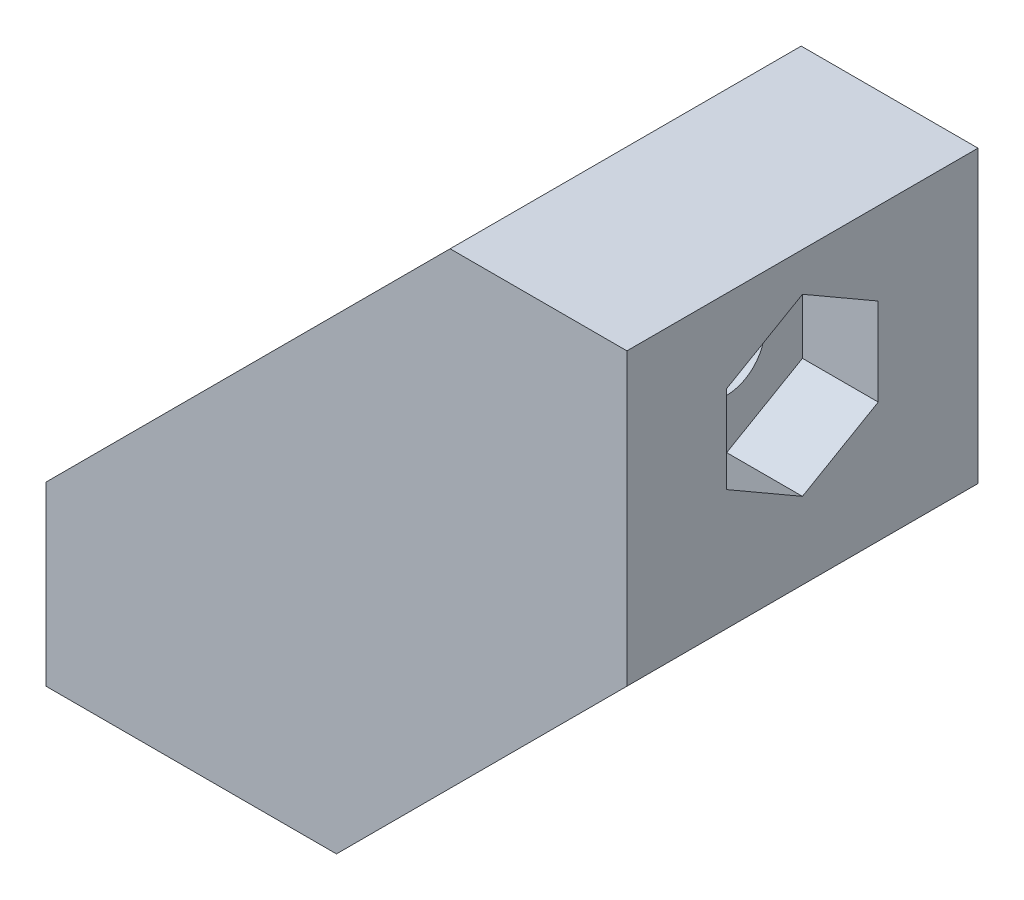
SolidWorks part; units mm, degrees
ref_plane "Front Plane" through (0, 0, 0) normal (0, 0, 1) x (1, 0, 0)
ref_plane "Top Plane" through (0, 0, 0) normal (0, 1, 0) x (1, 0, 0)
ref_plane "Right Plane" through (0, 0, 0) normal (1, 0, 0) x (0, 0, -1)
sketch "Sketch1" plane through (0, 0, 0) normal (0, 0, 1) x (1, 0, 0)
  line L0 (30, 0) -> (30, 6) construction
  line L2 (30, 0) -> (30, 8)
  line L3 (30, 8) -> (38, 8)
  line L5 (27, 0) -> (27, 6) construction
  line L6 (30, 0) -> (22, 0)
  line L8 (45, -7) -> (22, -7)
  line L9 (22, 0) -> (22, -7)
  line L11 (38, 8) -> (38, 16)
  line L12 (38, 16) -> (45, 16)
  line L13 (45, -7) -> (45, 16)
  line L14 (30, 6) -> (0, 6) construction
  line L15 (0, 0) -> (30, 0) construction
  line L16 (33.5, -7) -> (45, 4.5)
  dimension "D1" = 7
  dimension "D2" = 5
extrude "Boss-Extrude1" add sketch "Sketch1" against normal up to surface (7.9 mm away) contours L8 L16 L13 L12 L11 L3 L2 L6 L9 region at (35.0544, 2.9456, 0)
sketch "Sketch2" plane through (0, -7, 0) normal (0, -1, 0) x (1, 0, 0)
  circle A0 centre (27, -3.95) radius 1.5
  circle A1 centre (27, -3.95) radius 1.5 construction
extrude "Cut-Extrude1" cut sketch "Sketch2" against normal through all
sketch "Sketch3" plane through (38, -7, 0) normal (0, 1, 0) x (0, 0, -1)
  line L0 (0.95, 12.7321) -> (3.95, 14.4641)
  line L1 (3.95, 14.4641) -> (6.95, 12.7321)
  line L2 (6.95, 12.7321) -> (6.95, 9.2679)
  line L3 (6.95, 9.2679) -> (3.95, 7.5359)
  line L4 (3.95, 7.5359) -> (0.95, 9.2679)
  line L5 (0.95, 9.2679) -> (0.95, 12.7321)
  circle A0 centre (3.95, 11) radius 3.4641 construction
  circle A1 centre (3.95, 11) radius 1.5 construction
  point P7 (6.8792, 12.8492)
  point P10 (0, 0)
  dimension "D1" = 6
extrude "Cut-Extrude3" cut sketch "Sketch3" along normal blind 3
ref_plane "Plane1" through (19, 19, 0) normal (0.7071, 0.7071, 0) x (0.7071, -0.7071, 0)
sketch "Sketch4" plane through (0, 0, 0) normal (0, 0, 1) x (1, 0, 0)
  line L0 (22, 0) -> (38, 16)
  line L9 (22, -7) -> (33.5, -7)
  line L10 (33.5, -7) -> (45, 4.5)
  line L11 (45, 4.5) -> (45, 16)
  line L12 (45, 16) -> (38, 16)
  line L13 (38, 16) -> (38, 8)
  line L14 (38, 8) -> (30, 8)
  line L15 (30, 8) -> (30, 0)
  line L16 (30, 0) -> (22, 0)
  line L17 (22, 0) -> (22, -7)
  line L18 (22, -7) -> (33.5, -7)
  line L19 (33.5, -7) -> (45, 4.5)
  line L20 (45, 4.5) -> (45, 16)
  line L21 (45, 16) -> (38, 16)
  line L26 (22, 0) -> (22, -7)
  dimension "D1" = 0
extrude "Boss-Extrude2" add sketch "Sketch4" along normal blind 3
extrude "Boss-Extrude3" add sketch "Sketch4<3>" against normal blind 3 from surface starting at face at (33.7222, 4.2778, -7.9)
sketch "Sketch4<3>" plane through (0, 0, 0) normal (0, 0, 1) x (1, 0, 0) same geometry as "Sketch4"
sketch "Sketch5" plane through (0, 0, 0) normal (0, 1, 0) x (1, 0, 0)
  line L0 (22, 10.9) -> (22, 7.9) construction
  line L1 (22, 8.2) -> (30.3048, 8.2)
  line L2 (22, 8.2) -> (22, -0.3)
  line L3 (22, -0.3) -> (30.3048, -0.3)
  line L4 (30.3048, 8.2) -> (30.3048, -0.3)
  line L5 (30, 7.9) -> (22, 7.9) construction
  line L7 (30, 7.9) -> (30, 0) construction
  line L8 (30, 3.95) -> (30.3048, 3.95) construction
  dimension "D1" = 0.3
  dimension "D2" = 0.3048
extrude "Cut-Extrude4" cut sketch "Sketch5" along normal through all
mirror "Mirror1" about plane through (19, 19, 0) normal (0.7071, 0.7071, 0) of "Cut-Extrude4", "Cut-Extrude1", "Cut-Extrude3"
